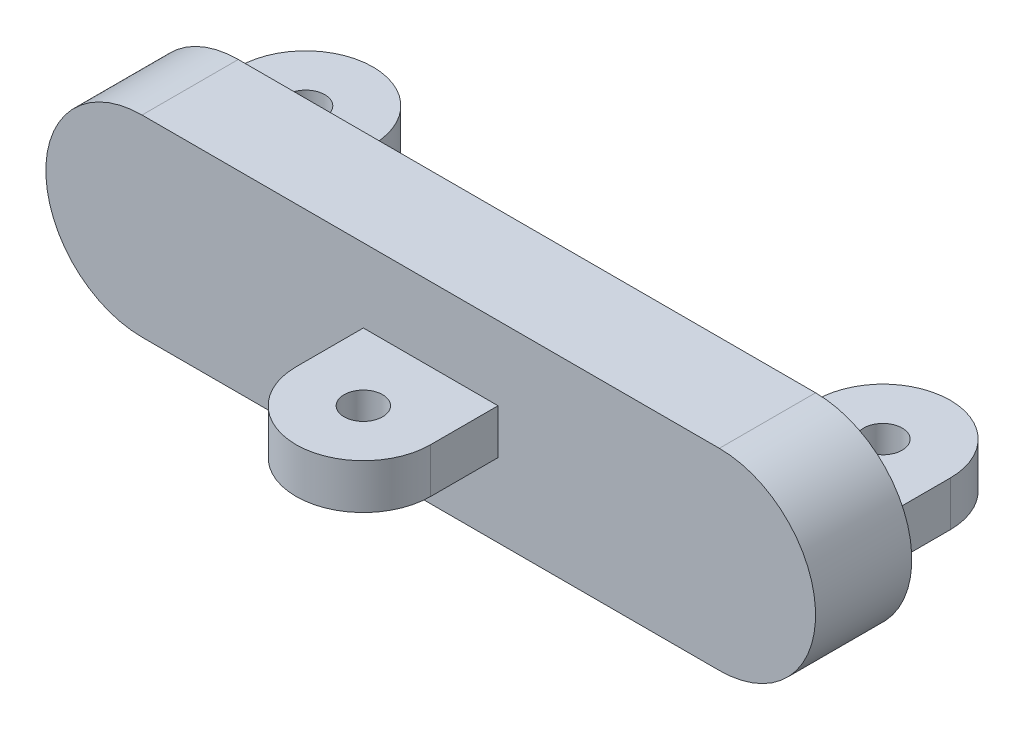
SolidWorks part; units mm, degrees
ref_plane "Front Plane" through (0, 0, 0) normal (0, 0, 1) x (1, 0, 0)
ref_plane "Top Plane" through (0, 0, 0) normal (0, 1, 0) x (1, 0, 0)
ref_plane "Right Plane" through (0, 0, 0) normal (1, 0, 0) x (0, 0, -1)
sketch "Sketch2" plane through (0, 0, 0) normal (0, 0, 1) x (1, 0, 0)
  line L1 (-15, -5) -> (15, -5)
  line L3 (-15, 5) -> (15, 5)
  line L5 (-15, -5) -> (15, 5) construction
  line L6 (-15, 5) -> (15, -5) construction
  arc A0 (-15, -5) -> (-15, 5) centre (-15, 0) cw
  arc A1 (15, -5) -> (15, 5) centre (15, 0) ccw
  point P0 (0, 0)
  dimension "D1" = 30
  dimension "D2" = 10
extrude "Boss-Extrude1" add sketch "Sketch2" against normal blind 5
sketch "Sketch3" plane through (0, 0, 0) normal (0, 0, 1) x (1, 0, 0)
  line L1 (-3.5, -1.1667) -> (3.5, -1.1667)
  line L2 (-3.5, -1.1667) -> (-3.5, 1.1667)
  line L3 (-3.5, 1.1667) -> (3.5, 1.1667)
  line L4 (3.5, -1.1667) -> (3.5, 1.1667)
  line L5 (-3.5, -1.1667) -> (3.5, 1.1667) construction
  line L6 (-3.5, 1.1667) -> (3.5, -1.1667) construction
  point P0 (0, 0)
  dimension "D1" = 2.3333
  dimension "D2" = 7
extrude "Boss-Extrude2" add sketch "Sketch3" along normal blind 3.5
sketch "Sketch6" plane through (0, 0, 3.5) normal (0, 0, 1) x (1, 0, 0)
  line L0 (0, 1.1667) -> (0, -1.1667)
  line L1 (3.5, 1.1667) -> (-3.5, 1.1667) construction
  line L2 (-3.5, -1.1667) -> (3.5, -1.1667) construction
  line L3 (0, -1.1667) -> (-3.5, -1.1667)
  line L4 (-3.5, -1.1667) -> (-3.5, 1.1667)
  line L5 (-3.5, 1.1667) -> (0, 1.1667)
revolve "Revolve1" add sketch "Sketch6" angle 180 about L0 reverse direction yes
sketch "Sketch7" plane through (0, 1.1667, 0) normal (0, 1, 0) x (1, 0, 0)
  circle A0 centre (0, -3.5) radius 1
  dimension "D1" = 2
  dimension "D2" = 3.5
extrude "Cut-Extrude1" cut sketch "Sketch7" against normal up to next contours A0
sketch "Sketch8" plane through (0, 0, -5) normal (0, 0, -1) x (-1, 0, 0)
  line L1 (0, 5.5) -> (0, -5.5) construction
  line L2 (-18.5, -1.165) -> (-11.5, -1.165)
  line L3 (-18.5, -1.165) -> (-18.5, 1.165)
  line L4 (-18.5, 1.165) -> (-11.5, 1.165)
  line L5 (-11.5, -1.165) -> (-11.5, 1.165)
  line L6 (-18.5, -1.165) -> (-11.5, 1.165) construction
  line L7 (-18.5, 1.165) -> (-11.5, -1.165) construction
  line L8 (18.5, 1.165) -> (11.5, -1.165) construction
  line L9 (18.5, -1.165) -> (11.5, 1.165) construction
  line L10 (11.5, -1.165) -> (11.5, 1.165)
  line L11 (18.5, 1.165) -> (11.5, 1.165)
  line L12 (18.5, -1.165) -> (18.5, 1.165)
  line L13 (18.5, -1.165) -> (11.5, -1.165)
  point P0 (-15, 0)
  point P13 (15, 0)
  dimension "D1" = 7
  dimension "D2" = 2.33
extrude "Boss-Extrude3" add sketch "Sketch8" along normal blind 3.5
sketch "Sketch9" plane through (0, 0, -8.5) normal (0, 0, -1) x (-1, 0, 0)
  line L0 (-18.5, -1.165) -> (-11.5, -1.165) construction
  line L1 (-18.5, 1.165) -> (-15, 1.165)
  line L2 (-18.5, 1.165) -> (-18.5, -1.165)
  line L3 (-18.5, -1.165) -> (-15, -1.165)
  line L4 (-15, 1.165) -> (-15, -1.165)
  line L5 (11.5, -1.165) -> (18.5, -1.165) construction
  line L6 (11.5, 1.165) -> (15, 1.165)
  line L7 (11.5, 1.165) -> (11.5, -1.165)
  line L8 (11.5, -1.165) -> (15, -1.165)
  line L9 (15, 1.165) -> (15, -1.165)
revolve "Revolve2" add sketch "Sketch9" angle 180 about L4 region at (16.75, 0, -8.5) reverse direction yes
revolve "Revolve3" add sketch "Sketch9<3>" angle 180 about L9 region at (-13.25, 0, -8.5) reverse direction yes
sketch "Sketch9<3>" plane through (0, 0, -8.5) normal (0, 0, -1) x (-1, 0, 0) same geometry as "Sketch9"
sketch "Sketch11" plane through (0, 1.165, 0) normal (0, 1, 0) x (1, 0, 0)
  line L0 (0, -5.5) -> (0, 5.5) construction
  circle A0 centre (-15, 8.5) radius 1
  circle A1 centre (15, 8.5) radius 1
  dimension "D1" = 2
extrude "Cut-Extrude2" cut sketch "Sketch11" against normal up to next
